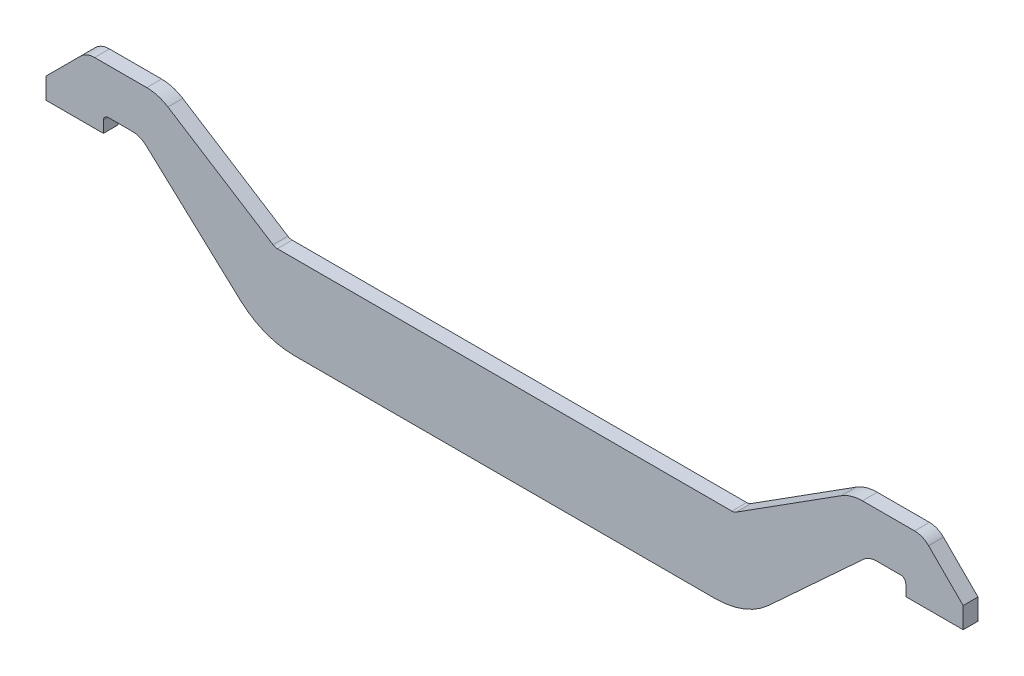
SolidWorks part; units mm, degrees
material "Alloy Steel"
ref_plane "Front Plane" through (0, 0, 0) normal (0, 0, 1) x (1, 0, 0)
ref_plane "Top Plane" through (0, 0, 0) normal (0, 1, 0) x (1, 0, 0)
ref_plane "Right Plane" through (0, 0, 0) normal (1, 0, 0) x (0, 0, -1)
sketch "Sketch1" plane through (0, 0, 0) normal (0, 0, 1) x (1, 0, 0)
  line L0 (-25.4657, 26.9875) -> (77.47, 26.9875) construction
  line L1 (-15.176, 0) -> (77.47, 0) construction
  line L2 (154.94, 0) -> (194.3735, 36.322)
  line L3 (-1086.8586, 36.322) -> (-69.6595, 36.322) construction
  line L4 (77.47, 0) -> (77.47, 100.6433) construction
  line L5 (0, 0) -> (154.94, 0)
  line L6 (206.1845, 36.322) -> (194.3735, 36.322)
  line L7 (3.81, 26.9875) -> (151.13, 26.9875)
  line L8 (206.1845, 31.115) -> (206.1845, 36.322)
  line L9 (-56.7055, 50.8) -> (-33.655, 50.8)
  line L10 (-69.6595, 37.846) -> (-69.6595, 36.322)
  line L11 (-51.2445, 36.322) -> (-39.4335, 36.322)
  line L12 (224.5995, 31.115) -> (206.1845, 31.115)
  line L13 (0, 0) -> (-39.4335, 36.322)
  line L14 (3.81, 26.9875) -> (-33.655, 50.8)
  line L15 (224.5995, 37.846) -> (224.5995, 31.115)
  line L16 (224.5995, 37.846) -> (211.6455, 50.8)
  line L17 (-69.6595, 37.846) -> (-56.7055, 50.8)
  line L18 (-69.6595, 37.846) -> (-69.6595, 31.115)
  line L19 (-51.2445, 31.115) -> (-51.2445, 36.322)
  line L20 (-69.6595, 31.115) -> (-51.2445, 31.115)
  line L21 (-56.7055, 50.8) -> (-33.655, 50.8) construction
  line L22 (-51.2445, 36.322) -> (-39.4335, 36.322) construction
  line L23 (211.6455, 50.8) -> (188.595, 50.8)
  line L24 (151.13, 26.9875) -> (188.595, 50.8)
  line L25 (-60.452, 31.115) -> (-60.452, 78.4909) construction
  dimension "D1" = 26.9875
  dimension "D2" = 36.322
  dimension "D3" = 50.8
  dimension "D4" = 137.922
  dimension "D5" = 77.47
  dimension "D6" = 30.226
  dimension "D7" = 31.115
  dimension "D8" = 73.66
  dimension "D9" = 135
  dimension "D10" = 111.125
  dimension "D11" = 6.731
  dimension "D12" = 18.415
extrude "Boss-Extrude1" add sketch "Sketch1" along normal blind 4.7625 contours L5 L7 | L7 L11 L14 | L9 L10 L11 region at (77.47, 21.0907, 0)
fillet "1.0 Radius" radius 25.4 2 edges at (0, 0, 2.3813) (154.94, 0, 2.3813)
fillet "0.1 Radius" radius 2.54 2 edges at (3.81, 26.9875, 2.3813) (151.13, 26.9875, 2.3813)
fillet "0.25 Radius" radius 6.35 4 edges at (194.3735, 36.322, 2.3813) (-39.4335, 36.322, 2.3813) (-56.7055, 50.8, 2.3813) (211.6455, 50.8, 2.3813)
fillet "0.5 Radius" radius 12.7 2 edges at (-33.655, 50.8, 2.3813) (188.595, 50.8, 2.3813)
fillet "0.0625 Radius" radius 1.5875 2 edges at (206.1845, 36.322, 2.3813) (-51.2445, 36.322, 2.3813)
